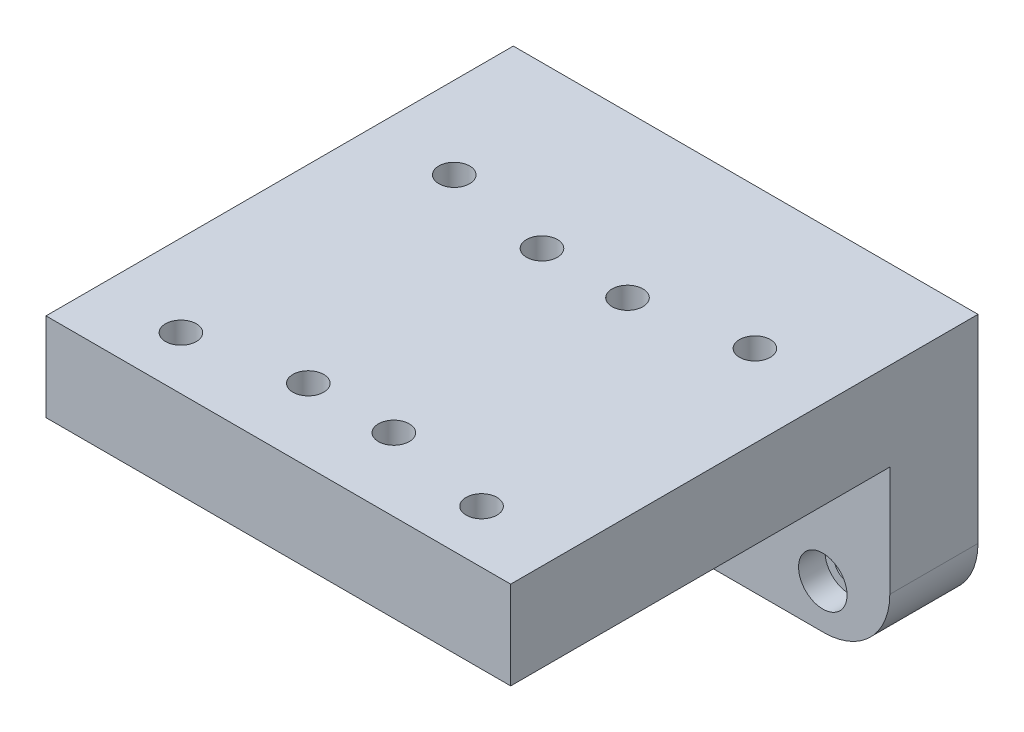
SolidWorks part; units mm, degrees
note: The reader was unsure of these and kept them because the rebuilt part matched: shared geometry of "Sketch3<4>".
ref_plane "Front Plane" through (0, 0, 0) normal (0, 0, 1) x (1, 0, 0)
ref_plane "Top Plane" through (0, 0, 0) normal (0, 1, 0) x (1, 0, 0)
ref_plane "Right Plane" through (0, 0, 0) normal (1, 0, 0) x (0, 0, -1)
sketch "Sketch1" plane through (0, 0, 0) normal (0, 1, 0) x (1, 0, 0)
  line L1 (-47.7, -38) -> (47.7, -38)
  line L2 (-47.7, -38) -> (-47.7, 38)
  line L3 (-47.7, 38) -> (47.7, 38)
  line L4 (47.7, -38) -> (47.7, 38)
  line L5 (-47.7, -38) -> (47.7, 38) construction
  line L6 (-47.7, 38) -> (47.7, -38) construction
  point P0 (0, 0)
  dimension "D1" = 76
  dimension "D2" = 95.4
extrude "Boss-Extrude1" add sketch "Sketch1" along normal blind 13
sketch "Sketch2" plane through (0, 13, 0) normal (0, 1, 0) x (1, 0, 0)
  line L0 (47.7, 38) -> (-47.7, 38) construction
  line L1 (-47.7, 38) -> (-47.7, -38) construction
  circle A0 centre (-34.1, 31) radius 3.5
  circle A2 centre (-9.7, 26.5) radius 3.5
  dimension "D1" = 7
  dimension "D2" = 7
  dimension "D3" = 13.6
  dimension "D4" = 38
  dimension "D5" = 11.5
extrude "Cut-Extrude1" cut sketch "Sketch2" against normal through all
mirror "Mirror1" about plane through (0, 0, 0) normal (1, 0, 0) of "Cut-Extrude1" second plane through (0, 0, 0) second plane normal (0, 0, 1)
sketch "Sketch3" plane through (0, 13, 0) normal (0, 1, 0) x (1, 0, 0)
  line L0 (-52.7, 63) -> (-52.7, -43)
  line L1 (-52.7, -43) -> (52.7, -43)
  line L2 (52.7, -43) -> (52.7, 63)
  line L3 (52.7, 63) -> (-52.7, 63)
  line L4 (0, 0) -> (0, -43) construction
  line L5 (-47.7, 38) -> (-47.7, -38) construction
  line L6 (-47.7, -38) -> (47.7, -38) construction
  line L7 (47.7, 38) -> (-47.7, 38) construction
  line L8 (-52.7, 43) -> (52.7, 43)
  dimension "D1" = 5
  dimension "D2" = 5
  dimension "D3" = 25
  dimension "D4" = 5
extrude "Boss-Extrude2" add sketch "Sketch3" against normal blind 20
extrude "Boss-Extrude3" add sketch "Sketch3<4>" against normal blind 60 contours L0 L8 L2 L3
sketch "Sketch3<4>" plane through (0, 13, 0) normal (0, 1, 0) x (1, 0, 0) same geometry as "Sketch3"
sketch "Sketch4" plane through (0, 0, -43) normal (0, 0, 1) x (1, 0, 0)
  line L0 (0, -7) -> (0, -47) construction
  line L1 (-37.5, -37) -> (37.5, -37)
  line L2 (-37.5, -37) -> (-37.5, -17)
  line L3 (-37.5, -17) -> (37.5, -17)
  line L4 (37.5, -37) -> (37.5, -17)
  line L5 (-37.5, -37) -> (37.5, -17) construction
  line L6 (-37.5, -17) -> (37.5, -37) construction
  line L8 (-52.7, -7) -> (52.7, -7) construction
  line L9 (-52.7, -47) -> (52.7, -47) construction
  point P0 (0, -27)
  point P10 (12.4197, -32.1051)
  point P11 (52.7, -23.8518)
  point P14 (28.3034, -19.8809)
  point P16 (0, -27)
  point P17 (52.7, -23.8518)
  dimension "D1" = 75
  dimension "D2" = 20
hole_wizard "CBORE for M6 SHCS1" positions "3DSketch1" profile "Sketch6" counterbore size "M6" standard "ANSI Metric" end condition through all
sketch3d "3DSketch1"
  point P6 (37.5, -37, -43)
  point P9 (-37.5, -37, -43)
  point P18 (0, 0, 0)
  point P19 (0, 0, 0)
  point P20 (0, 0, 0)
  point P21 (0, 0, 0)
sketch "Sketch6" plane through (37.5, -37, -43) normal (1, 0, 0) x (0, -1, 0)
  line L0 (0, 0) -> (0, 20)
  line L1 (0, 20) -> (3.5, 20)
  line L3 (3.5, 20) -> (3.5, 6)
  line L4 (3.5, 6) -> (5.5, 6)
  line L5 (5.5, 6) -> (5.5, 0)
  line L7 (5.5, 0) -> (0, 0)
  line L11 (0, -6.35) -> (0, 107.95) construction
  dimension "Thru Hole Dia." = 7
  dimension "Thru Hole Depth" = 20
  dimension "C'Bore Dia." = 11
  dimension "C'Bore Depth" = 6
fillet "Fillet1" radius 15 2 edges at (-52.7, -47, -53) (52.7, -47, -53)
